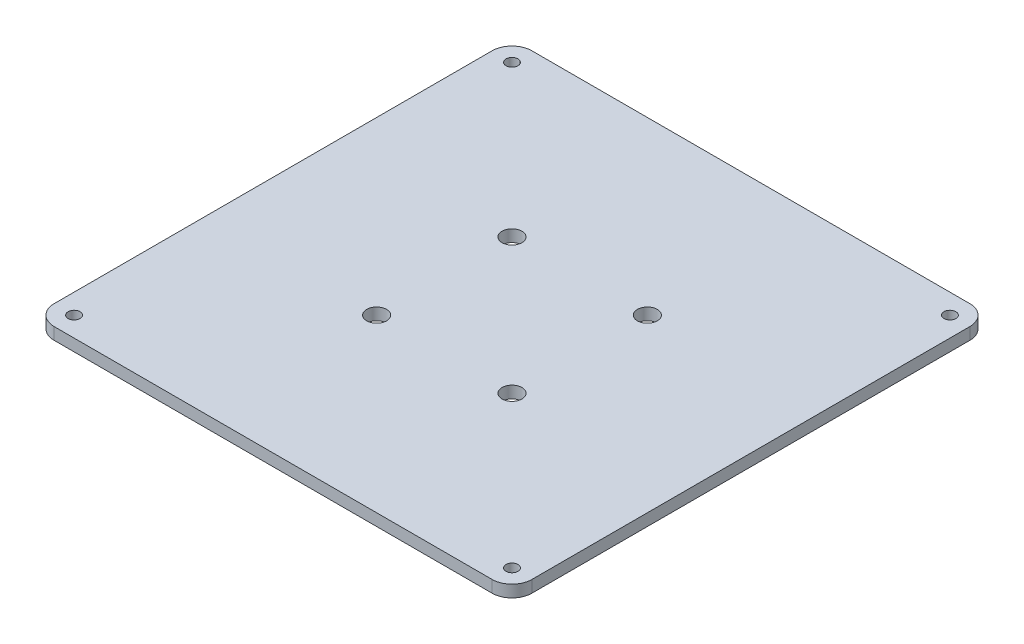
SolidWorks part; units mm, degrees
material "ABS"
ref_plane "Alzado" through (0, 0, 0) normal (0, 0, 1) x (1, 0, 0)
ref_plane "Planta" through (0, 0, 0) normal (0, 1, 0) x (1, 0, 0)
ref_plane "Vista lateral" through (0, 0, 0) normal (1, 0, 0) x (0, 0, -1)
sketch "Sketch1" plane through (0, 0, 0) normal (0, 1, 0) x (1, 0, 0)
  line L1 (-17, -17) -> (17, -17) construction
  line L2 (-17, -17) -> (-17, 17) construction
  line L3 (-17, 17) -> (17, 17) construction
  line L4 (17, -17) -> (17, 17) construction
  line L5 (-17, -17) -> (17, 17) construction
  line L6 (-17, 17) -> (17, -17) construction
  line L7 (-60, -60) -> (60, -60)
  line L8 (-60, -60) -> (-60, 60)
  line L9 (-60, 60) -> (60, 60)
  line L10 (60, -60) -> (60, 60)
  line L11 (-60, -60) -> (60, 60) construction
  line L12 (-60, 60) -> (60, -60) construction
  circle A0 centre (-17, -17) radius 2.5
  circle A1 centre (17, 17) radius 2.5
  circle A2 centre (17, -17) radius 2.5
  circle A3 centre (-17, 17) radius 2.5
  point P0 (0, 0)
  point P10 (0, 0)
  point P15 (0, 0)
  dimension "D3" = 5
  dimension "D1" = 34
  dimension "D4" = 120
  dimension "D5" = 120
extrude "Boss-Extrude1" add sketch "Sketch1" along normal blind 3
fillet "Fillet1" radius 5 4 edges at (-60, 1.5, -60) (60, 1.5, -60) (60, 1.5, 60) (-60, 1.5, 60)
sketch "Sketch2" plane through (0, 3, 0) normal (0, 1, 0) x (1, 0, 0)
  line L0 (-55, 55) -> (-55, 60) construction
  line L1 (-55, 55) -> (-60, 55) construction
  circle A0 centre (-55, 55) radius 1.5
  dimension "D1" = 3
extrude "Cut-Extrude1" cut sketch "Sketch2" against normal through all
mirror "Mirror3" about plane through (0, 0, 0) normal (0, 0, 1) of "Cut-Extrude1" second plane through (0, 0, 0) second plane normal (1, 0, 0)
